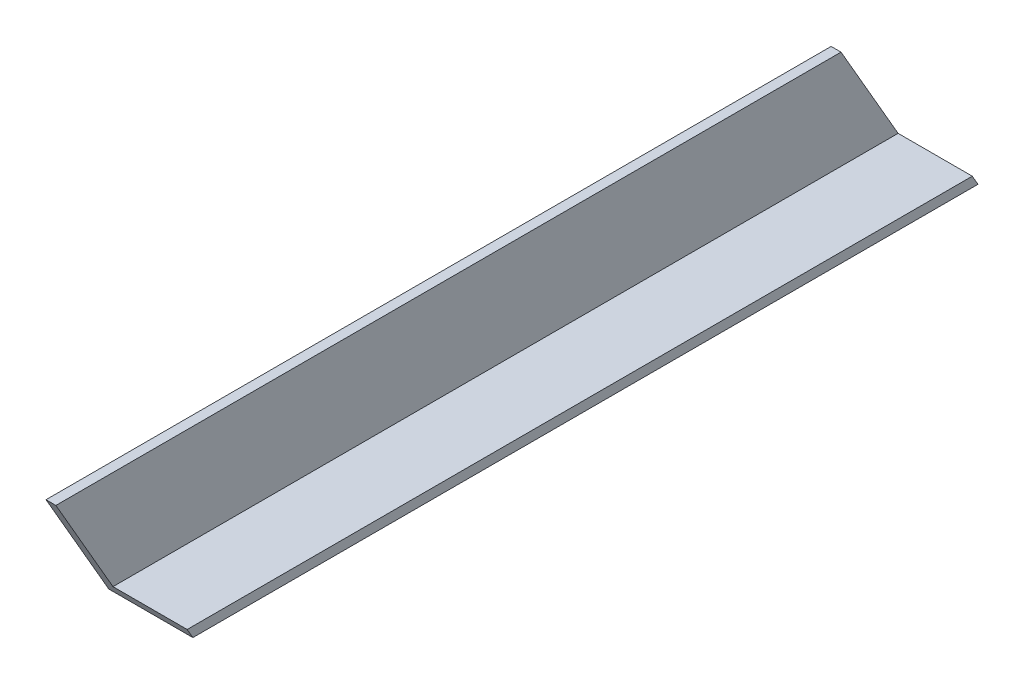
SolidWorks part; units mm, degrees
ref_plane "Front Plane" through (0, 0, 0) normal (0, 0, 1) x (1, 0, 0)
ref_plane "Top Plane" through (0, 0, 0) normal (0, 1, 0) x (1, 0, 0)
ref_plane "Right Plane" through (0, 0, 0) normal (1, 0, 0) x (0, 0, -1)
sketch "Sketch1" plane through (0, 0, 0) normal (0, 0, 1) x (1, 0, 0)
  line L0 (0, 0) -> (0, 22)
  line L1 (0, 22) -> (2, 22)
  line L2 (2, 22) -> (2, 2)
  line L3 (2, 2) -> (17, 2)
  line L4 (17, 2) -> (17, 0)
  line L5 (17, 0) -> (0, 0)
  dimension "D1" = 22
  dimension "D2" = 17
  dimension "D3" = 2
  dimension "D4" = 2
extrude "Boss-Extrude1" add sketch "Sketch1" along normal blind 250
sketch "Sketch2" plane through (17, 0, 0) normal (1, 0, 0) x (0, 0, -1)
  line L1 (-171.473, 22) -> (-250, 22)
  line L5 (-250, 22) -> (-250, 0)
  line L8 (-12.7017, 22) -> (0, 22)
  line L9 (-250, 22) -> (0, 22) construction
  line L10 (0, 22) -> (0, 0)
  line L11 (0, 0) -> (-12.7017, 22)
  line L12 (-171.473, 22) -> (-158.7713, 0)
  line L13 (-250, 0) -> (0, 0) construction
  line L14 (-250, 0) -> (-158.7713, 0)
  dimension "D1" = 30
  dimension "D2" = 137.5
extrude "Cut-Extrude1" cut sketch "Sketch2" against normal blind 150
